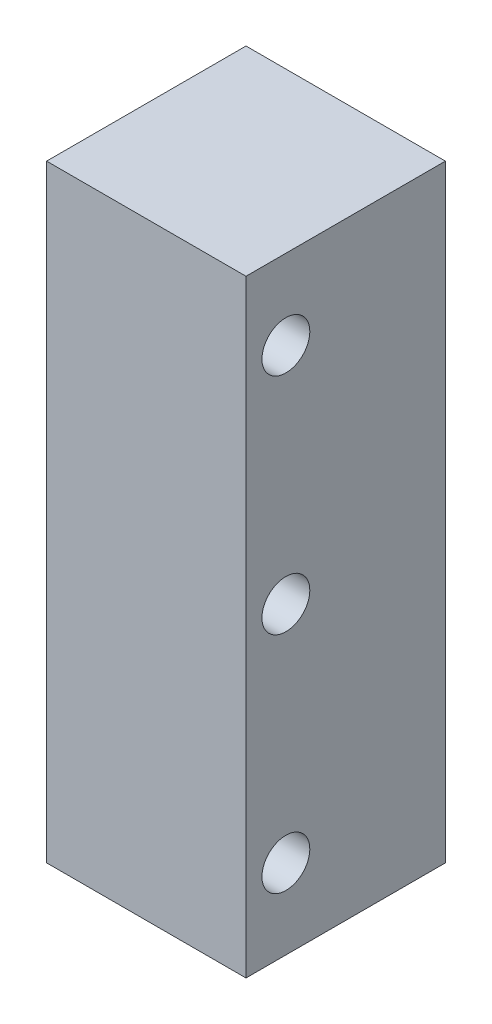
SolidWorks part; units mm, degrees
ref_plane "Front Plane" through (0, 0, 0) normal (0, 0, 1) x (1, 0, 0)
ref_plane "Top Plane" through (0, 0, 0) normal (0, 1, 0) x (1, 0, 0)
ref_plane "Right Plane" through (0, 0, 0) normal (1, 0, 0) x (0, 0, -1)
sketch "Sketch1" plane through (0, 0, 0) normal (0, 0, 1) x (1, 0, 0)
  line L1 (-25, 76.2) -> (25, 76.2)
  line L2 (-25, 76.2) -> (-25, -76.2)
  line L3 (-25, -76.2) -> (25, -76.2)
  line L4 (25, 76.2) -> (25, -76.2)
  line L5 (-25, 76.2) -> (25, -76.2) construction
  line L6 (-25, -76.2) -> (25, 76.2) construction
  point P0 (0, 0)
  dimension "D1" = 50
extrude "Boss-Extrude1" add sketch "Sketch1" along normal blind 50
sketch "Sketch2" plane through (25, 0, 0) normal (1, 0, 0) x (0, 0, -1)
  line L0 (-50, -76.2) -> (-50, 76.2) construction
  line L1 (-50, 76.2) -> (0, 76.2) construction
  line L2 (-50, -76.2) -> (0, -76.2) construction
  circle A0 centre (-40, 56.2) radius 6
  circle A1 centre (-40, 0) radius 6
  circle A2 centre (-40, -56.2) radius 6
  dimension "D1" = 10
  dimension "D2" = 10
  dimension "D3" = 10
  dimension "D4" = 20
  dimension "D5" = 20
  dimension "D6" = 112.4
  dimension "D7" = 56.2
extrude "Cut-Extrude1" cut sketch "Sketch2" against normal through all
sketch "Sketch4" plane through (0, 76.2, 0) normal (0, 1, 0) x (1, 0, 0)
  line L0 (25, 0) -> (-25, 0) construction
  line L1 (-25, -50) -> (-25, 0) construction
  line L2 (25, -50) -> (25, 0) construction
  circle A0 centre (-5, -10) radius 6
  circle A1 centre (51.2, -10) radius 6
  circle A2 centre (5, -10) radius 6
  dimension "D1" = 12
  dimension "D2" = 10
  dimension "D3" = 20
  dimension "D4" = 20
  dimension "D5" = 10
  dimension "D6" = 10
  dimension "D7" = 10
  dimension "D8" = 56.2
extrude "Cut-Extrude2" cut sketch "Sketch4" against normal through all rebuild error yes
